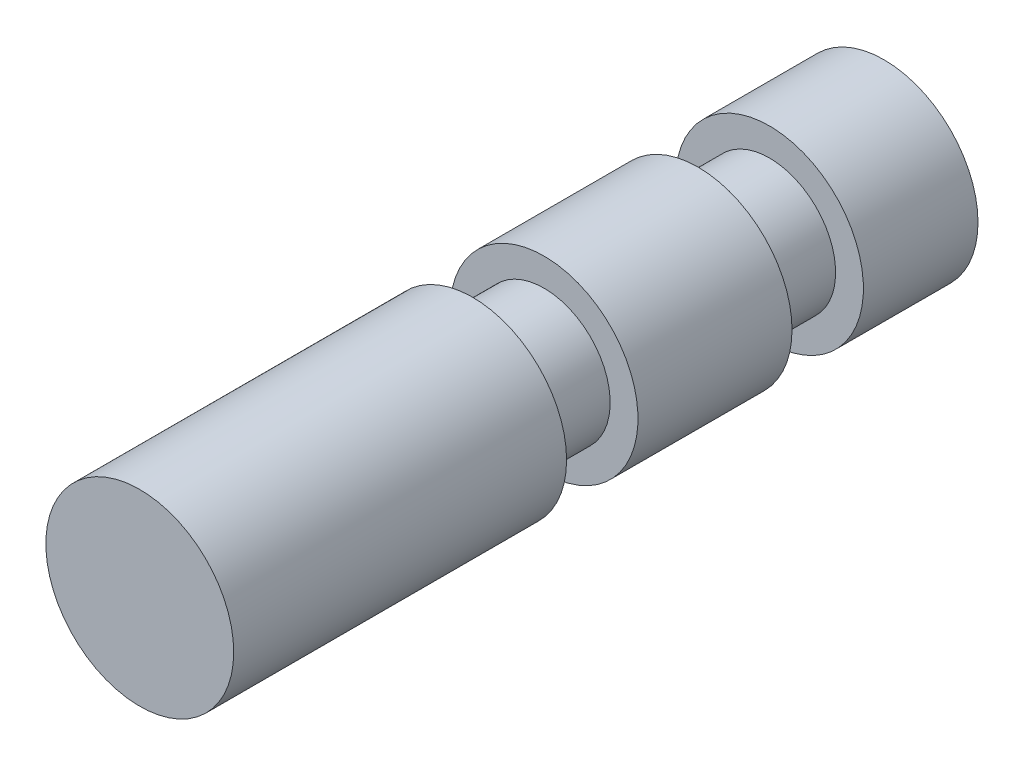
SolidWorks part; units mm, degrees
material "AISI 1015 Steel, Cold Drawn (SS)"
ref_plane "Front Plane" through (0, 0, 0) normal (0, 0, 1) x (1, 0, 0)
ref_plane "Top Plane" through (0, 0, 0) normal (0, 1, 0) x (1, 0, 0)
ref_plane "Right Plane" through (0, 0, 0) normal (1, 0, 0) x (0, 0, -1)
sketch "Sketch1" plane through (0, 0, 0) normal (0, 0, 1) x (1, 0, 0)
  circle A0 centre (0, 0) radius 3.175
  dimension "D1" = 6.35
extrude "Boss-Extrude1" add sketch "Sketch1" along normal blind 25.1587
sketch "Sketch3" plane through (0, 0, 0) normal (0, 1, 0) x (1, 0, 0)
  circle A0 centre (0, -3.175) radius 1.397
  dimension "D1" = 2.794
  dimension "D2" = 3.175
extrude "Cut-Extrude1" [suppressed] cut sketch "Sketch3" against normal through all and the other way through all
sketch "Sketch4" plane through (0, 0, 0) normal (1, 0, 0) x (0, 0, -1)
  line L0 (0, 0) -> (-25.1587, 0) construction
  line L1 (-5.08, 0) -> (-5.08, 2.9464) construction
  line L3 (-6.2865, 3.6576) -> (-3.8735, 3.6576)
  line L4 (-25.1587, 3.175) -> (-25.1587, -3.175) construction
  line L5 (-6.2865, 3.6576) -> (-6.2865, 2.2352)
  line L6 (-6.2865, 2.2352) -> (-3.8735, 2.2352)
  line L7 (-3.8735, 3.6576) -> (-3.8735, 2.2352)
  line L8 (-6.2865, 3.6576) -> (-3.8735, 2.2352) construction
  line L9 (-6.2865, 2.2352) -> (-3.8735, 3.6576) construction
  point P3 (-5.08, 0)
  point P11 (-5.08, 0)
  dimension "D3" = 2.413
  dimension "D1" = 5.08
  dimension "D2" = 2.2352
  dimension "D4" = 1.4224
  dimension "D5" = 3.6576
sketch "Sketch6" plane through (0, 0, 0) normal (0, 0, -1) x (-1, 0, 0)
  circle A0 centre (0, 0) radius 0.635
  dimension "D1" = 1.27
extrude "Cut-Extrude2" [suppressed] cut sketch "Sketch6" against normal up to surface (35.56 mm away) up to face at (3.175, 0, 25.1587)
sketch "Sketch9" plane through (0, 0, 0) normal (0, 0, -1) x (-1, 0, 0)
  circle A0 centre (0, 0) radius 1.397
extrude "Cut-Extrude3" cut sketch "Sketch9" against normal blind 7.62
revolve "Cut-Revolve1" cut sketch "Sketch4" angle 360 about L0
pattern_linear "LPattern1" count 2 spacing 7.62 along (0, 0, 1) of "Cut-Revolve1"
equation "\"D1@Boss-Extrude1\"=1.190500in-0.2in"
equation "\"D2@Sketch4\"=0.176/2"
